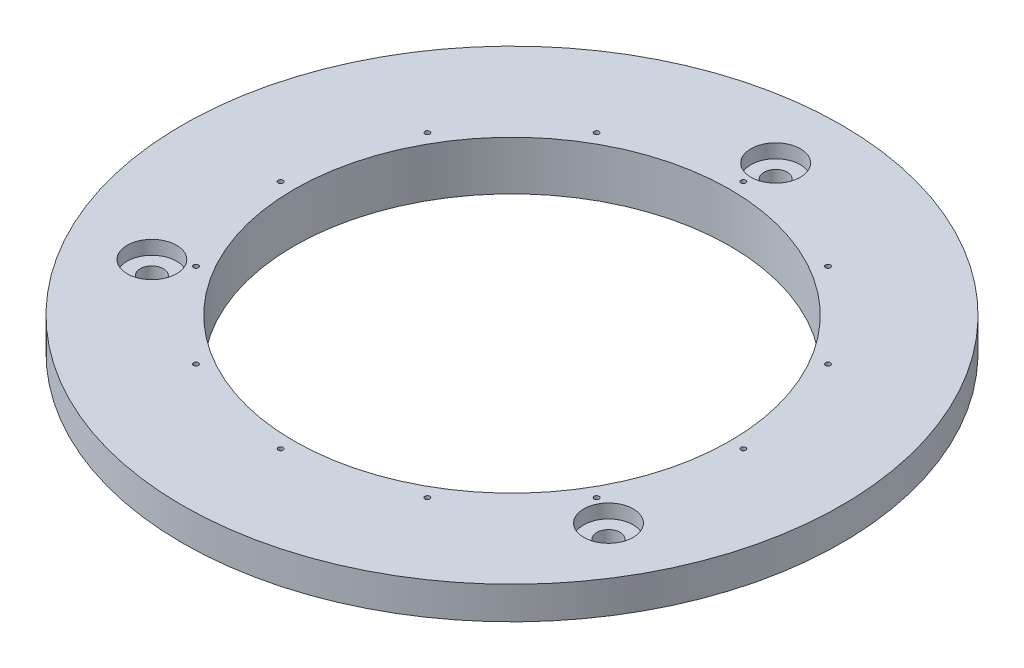
SolidWorks part; units mm, degrees
note: '?' marks a value the reader was unsure of.
material "6061 Alloy"
ref_plane "Front Plane" through (0, 0, 0) normal (0, 0, 1) x (1, 0, 0)
ref_plane "Top Plane" through (0, 0, 0) normal (0, 1, 0) x (1, 0, 0)
ref_plane "Right Plane" through (0, 0, 0) normal (1, 0, 0) x (0, 0, -1)
sketch "Sketch2" plane through (0, 0, 0) normal (0, 1, 0) x (1, 0, 0)
  circle A0 centre (0, 0) radius 63.5
  circle A1 centre (0, 0) radius 42
  dimension "D1" = 127
  dimension "D2" = 84
extrude "Boss-Extrude1" add sketch "Sketch2" along normal blind 9.45
sketch "Sketch15" [suppressed] plane through (0, 9.45, 0) normal (0, 1, 0) x (1, 0, 0)
  line L1 (6.244, 55) -> (-50.7534, -22.0925)
  line L2 (-50.7534, -22.0925) -> (44.5094, -32.9075)
  line L3 (44.5094, -32.9075) -> (6.244, 55)
  circle A0 centre (0, 0) radius 27.6766 construction
hole_wizard "CBORE for M5 Hex Head Bolt1" [suppressed] positions "3DSketch8" profile "Sketch16" counterbore size "M5" standard "ANSI Metric"
sketch3d "3DSketch8" [suppressed]
  point P0 (6.244, 9.45, -55)
  point P3 (44.5094, 9.45, 32.9075)
  point P6 (-50.7534, 9.45, 22.0925)
sketch "Sketch16" plane through (6.244, 9.45, -55) normal (1, 0, 0) x (0, 0, 1)
  line L0 (0, 0) -> (0, 21.4024)
  line L1 (0, 21.4024) -> (2.75, 19.75)
  line L2 (2.75, 19.75) -> (2.75, 3.58)
  line L3 (2.75, 3.58) -> (6.12, 3.58)
  line L4 (6.12, 3.58) -> (6.12, 0)
  line L5 (6.12, 0) -> (0, 0)
  line L10 (0, 21.4024) -> (-2.75, 19.75) construction
  line L11 (0, -6.35) -> (0, 107.95) construction
  dimension "Hole Dia." = 5.5
  dimension "Hole Depth" = 19.75
  dimension "C'Bore Dia." = 12.24
  dimension "C'Bore Depth" = 3.58
  dimension "Drill Angle" = 118
sketch "Sketch26" plane through (0, 0, 0) normal (0, 1, 0) x (1, 0, 0)
  circle A0 centre (0, 0) radius 63.5
  dimension "D1" = 127
ref_axis "Axis1" through (0, 9.45, 0) along (0, -1, 0)?
sketch "Sketch27" plane through (0, 0, 0) normal (0, 0, 1) x (1, 0, 0)
  line L0 (63.5, 0) -> (-63.5, 0) construction
  line L1 (63.5, 0) -> (58.5912, 0)
  line L2 (63.5, 0) -> (63.5, 3.175)
  line L3 (63.5, 3.175) -> (58.5912, 3.175)
  line L4 (58.5912, 0) -> (58.5912, 3.175)
  line L5 (69.85, 0) -> (-69.85, 0) construction
  line L6 (63.5, 0) -> (63.5, 9.45) construction
  line L7 (63.5, 0) -> (63.5, 9.45)
  line L8 (0, 9.45) -> (0, 0) construction
  line L9 (0, 0) -> (0, 15.4643) construction
  dimension "D1" = 117.1823
  dimension "D2" = 3.175
revolve "Cut-Revolve1" cut sketch "Sketch27" angle 360 about L9
hole_wizard "M1.2x0.25 Tapped Hole1" [suppressed] positions "Sketch28" profile "Sketch29" tap size "M1.2x0.25" standard "ANSI Metric"
sketch "Sketch28" [suppressed] plane through (-17.102, 9.45, -64.2994) normal (0, 1, 0) x (0.108, 0, -0.9941)
  point P0 (-95.0061, 8.4911)
  point P3 (-74.3741, 20.6104)
  point P6 (-50.4466, 20.79)
  point P9 (-29.6349, 8.9817)
  point P12 (-17.5156, -11.6503)
  point P15 (-17.3361, -35.5778)
  point P18 (-29.1443, -56.3895)
  point P21 (-49.7764, -68.5087)
  point P24 (-73.7039, -68.6883)
  point P27 (-94.5155, -56.8801)
  point P30 (-106.6348, -36.248)
  point P33 (-106.8144, -12.3205)
sketch "Sketch29" plane through (-35.8084, 9.45, 29.2331) normal (1, 0, 0) x (0, 0, 1)
  line L0 (0, 0) -> (0, 9.45)
  line L1 (0, 9.45) -> (0.475, 9.45)
  line L2 (0.475, 9.45) -> (0.475, 0)
  line L3 (0.475, 0) -> (0, 0)
  line L4 (0, -6.35) -> (0, 107.95) construction
  dimension "Thru Tap Drill Dia." = 0.95
  dimension "Thru Tap Drill Depth" = 9.45
cosmetic thread "Hole Thread1" [suppressed] parameters "D2"=1.2
cosmetic thread "Hole Thread2" [suppressed] parameters "D2"=1.2
cosmetic thread "Hole Thread3" [suppressed] parameters "D2"=1.2
cosmetic thread "Hole Thread4" [suppressed] parameters "D2"=1.2
cosmetic thread "Hole Thread5" [suppressed] parameters "D2"=1.2
cosmetic thread "Hole Thread6" [suppressed] parameters "D2"=1.2
cosmetic thread "Hole Thread7" [suppressed] parameters "D2"=1.2
cosmetic thread "Hole Thread8" [suppressed] parameters "D2"=1.2
cosmetic thread "Hole Thread9" [suppressed] parameters "D2"=1.2
cosmetic thread "Hole Thread10" [suppressed] parameters "D2"=1.2
cosmetic thread "Hole Thread11" [suppressed] parameters "D2"=1.2
cosmetic thread "Hole Thread12" [suppressed] parameters "D2"=1.2
sketch "Sketch31" plane through (0, 9.45, 0) normal (0, 1, 0) x (1, 0, 0)
  line L1 (0, -63.5) -> (0, 63.5)
  circle A1 centre (0, 0) radius 63.5 construction
hole_wizard "CBORE for #8 Binding Head Machine Screw1" positions "3DSketch10" profile "Sketch33" counterbore size "#8" standard "ANSI Inch"
sketch3d "3DSketch10"
  line L0 (0, 9.45, 63.5) -> (0, 9.45, -63.5) construction
  line L1 (0, 9.45, 0) -> (0, 0, 0) construction
  point P0 (0, 9.45, -50.8)
  dimension "D1" = 50.8
sketch "Sketch33" plane through (0, 9.45, -50.8) normal (1, 0, 0) x (0, 0, 1)
  line L0 (0, 0) -> (0, 503.0007)
  line L1 (0, 503.0007) -> (2.2479, 501.65)
  line L2 (2.2479, 501.65) -> (2.2479, 2.667)
  line L3 (2.2479, 2.667) -> (4.7625, 2.667)
  line L4 (4.7625, 2.667) -> (4.7625, 0)
  line L5 (4.7625, 0) -> (0, 0)
  line L10 (0, 503.0007) -> (-2.2479, 501.65) construction
  line L11 (0, -6.35) -> (0, 107.95) construction
  dimension "Hole Dia." = 4.4958
  dimension "Hole Depth" = 501.65
  dimension "C'Bore Dia." = 9.525
  dimension "C'Bore Depth" = 2.667
  dimension "Drill Angle" = 118
pattern_circular "CirPattern1" count 3 over 360 about axis through (0, 0, 0) along (0, 1, 0) of "CBORE for #8 Binding Head Machine Screw1"
hole_wizard "M1.2x0.25 Tapped Hole2" positions "3DSketch11" profile "Sketch34" tap size "M1.2x0.25" standard "ANSI Metric" end condition through all
sketch3d "3DSketch11"
  line L0 (0, 9.45, 63.5) -> (0, 9.45, -63.5) construction
  point P0 (0, 9.45, -44.5799)
cosmetic thread "Hole Thread13" parameters "D2"=1.2
sketch "Sketch34" plane through (0, 9.45, -44.5799) normal (1, 0, 0) x (0, 0, 1)
  line L0 (0, 0) -> (0, 9.45)
  line L1 (0, 9.45) -> (0.475, 9.45)
  line L2 (0.475, 9.45) -> (0.475, 0)
  line L5 (0.475, 0) -> (0, 0)
  line L11 (0, -6.35) -> (0, 107.95) construction
  dimension "Thru Tap Drill Dia." = 0.95
  dimension "Thru Tap Drill Depth" = 9.45
pattern_circular "CirPattern2" count 12 over 360 about axis through (0, 0, 0) along (0, 1, 0) of "M1.2x0.25 Tapped Hole2"
cosmetic thread "Hole Thread14" parameters "D2"=1.2
cosmetic thread "Hole Thread15" parameters "D2"=1.2
cosmetic thread "Hole Thread16" parameters "D2"=1.2
cosmetic thread "Hole Thread17" parameters "D2"=1.2
cosmetic thread "Hole Thread18" parameters "D2"=1.2
cosmetic thread "Hole Thread19" parameters "D2"=1.2
cosmetic thread "Hole Thread20" parameters "D2"=1.2
cosmetic thread "Hole Thread21" parameters "D2"=1.2
cosmetic thread "Hole Thread22" parameters "D2"=1.2
cosmetic thread "Hole Thread23" parameters "D2"=1.2
cosmetic thread "Hole Thread24" parameters "D2"=1.2
sketch "Sketch35" plane through (0, 0, 0) normal (0, -1, 0) x (1, 0, 0)
  circle A2 centre (43.9941, 25.4) radius 4.3688
  dimension "D1" = 8.7376
equation "\"ODia\"= 5in"
equation "\"IDiam\"= 84mm"
equation "\"Thick\"= 9.45mm"
equation "\"Lip\"= 3.29mm"
equation "\"D1@Boss-Extrude1\"=\"Thick\""
